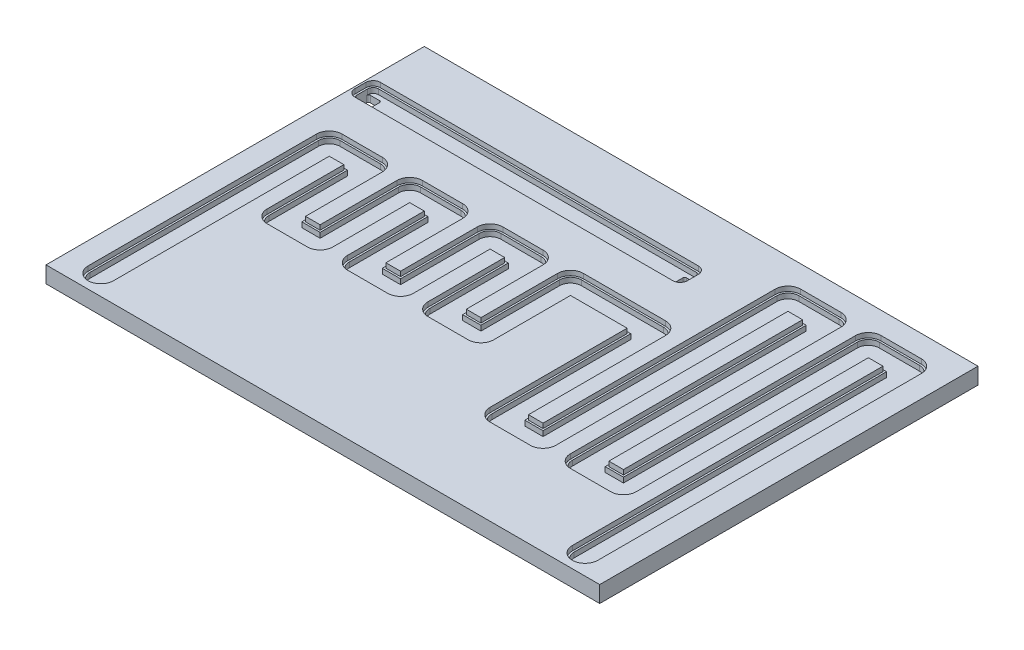
SolidWorks part; units mm, degrees
ref_plane "前视基准面" through (0, 0, 0) normal (0, 0, 1) x (1, 0, 0)
ref_plane "上视基准面" through (0, 0, 0) normal (0, 1, 0) x (1, 0, 0)
ref_plane "右视基准面" through (0, 0, 0) normal (1, 0, 0) x (0, 0, -1)
sketch "草图1" plane through (0, 0, 0) normal (0, 1, 0) x (1, 0, 0)
  line L0 (5, -195) -> (5, -165)
  line L1 (0, 0) -> (1515, 0)
  line L2 (0, 0) -> (0, -1035)
  line L3 (0, -1035) -> (1515, -1035)
  line L4 (1515, 0) -> (1515, -1035)
  line L5 (25, -145) -> (895, -145)
  line L6 (915, -165) -> (915, -195)
  line L7 (895, -215) -> (25, -215)
  line L8 (-125.9274, -180) -> (1036.3031, -180) construction
  line L9 (25, -150) -> (895, -150)
  line L10 (910, -165) -> (910, -195)
  line L11 (895, -210) -> (25, -210)
  line L12 (10, -195) -> (10, -165)
  line L13 (60, -980) -> (60, -355)
  line L14 (40, -197.5) -> (15, -197.5)
  line L15 (45, -192.5) -> (45, -167.5)
  line L16 (40, -162.5) -> (15, -162.5)
  line L17 (10, -192.5) -> (10, -167.5)
  line L18 (45, -197.5) -> (10, -162.5) construction
  line L19 (45, -162.5) -> (10, -197.5) construction
  line L20 (905, -197.5) -> (880, -197.5)
  line L21 (910, -192.5) -> (910, -167.5)
  line L22 (905, -162.5) -> (880, -162.5)
  line L23 (875, -192.5) -> (875, -167.5)
  line L24 (910, -197.5) -> (875, -162.5) construction
  line L25 (910, -162.5) -> (875, -197.5) construction
  line L26 (95, -320) -> (205, -320)
  line L27 (240, -355) -> (240, -565)
  line L28 (240, -565) -> (280, -565)
  line L29 (280, -565) -> (280, -355)
  line L30 (315, -320) -> (425, -320)
  line L31 (460, -355) -> (460, -565)
  line L32 (460, -565) -> (500, -565)
  line L33 (500, -565) -> (500, -355)
  line L34 (535, -320) -> (645, -320)
  line L35 (680, -355) -> (680, -565)
  line L36 (680, -565) -> (720, -565)
  line L37 (720, -565) -> (720, -355)
  line L38 (755, -320) -> (980, -320)
  line L39 (1015, -355) -> (1015, -730)
  line L40 (1015, -730) -> (1055, -730)
  line L41 (1055, -730) -> (1055, -95)
  line L42 (1090, -60) -> (1200, -60)
  line L43 (1235, -95) -> (1235, -730)
  line L44 (1235, -730) -> (1275, -730)
  line L45 (1275, -730) -> (1275, -95)
  line L46 (1310, -60) -> (1420, -60)
  line L47 (1455, -95) -> (1455, -980)
  line L48 (1455, -980) -> (1385, -980) construction
  line L49 (1385, -980) -> (1385, -130)
  line L50 (1385, -130) -> (1345, -130)
  line L51 (1345, -130) -> (1345, -765)
  line L52 (1310, -800) -> (1200, -800)
  line L53 (1165, -765) -> (1165, -130)
  line L54 (1165, -130) -> (1125, -130)
  line L55 (1125, -130) -> (1125, -765)
  line L56 (1090, -800) -> (980, -800)
  line L57 (945, -765) -> (945, -390)
  line L58 (945, -390) -> (790, -390)
  line L59 (790, -390) -> (790, -600)
  line L60 (755, -635) -> (645, -635)
  line L61 (610, -600) -> (610, -390)
  line L62 (610, -390) -> (570, -390)
  line L63 (570, -390) -> (570, -600)
  line L64 (535, -635) -> (425, -635)
  line L65 (390, -600) -> (390, -390)
  line L66 (390, -390) -> (350, -390)
  line L67 (350, -390) -> (350, -600)
  line L68 (315, -635) -> (205, -635)
  line L69 (170, -600) -> (170, -390)
  line L70 (170, -390) -> (130, -390)
  line L71 (130, -390) -> (130, -980)
  line L72 (130, -980) -> (60, -980) construction
  line L73 (1390, -980) -> (1390, -125)
  line L74 (1390, -125) -> (1340, -125)
  line L75 (1340, -125) -> (1340, -765)
  line L76 (1310, -795) -> (1200, -795)
  line L77 (1170, -765) -> (1170, -125)
  line L78 (1170, -125) -> (1120, -125)
  line L79 (1120, -125) -> (1120, -765)
  line L80 (1090, -795) -> (980, -795)
  line L81 (950, -765) -> (950, -385)
  line L82 (950, -385) -> (785, -385)
  line L83 (785, -385) -> (785, -600)
  line L84 (755, -630) -> (645, -630)
  line L85 (615, -600) -> (615, -385)
  line L86 (615, -385) -> (565, -385)
  line L87 (565, -385) -> (565, -600)
  line L88 (535, -630) -> (425, -630)
  line L89 (395, -600) -> (395, -385)
  line L90 (395, -385) -> (345, -385)
  line L91 (345, -385) -> (345, -600)
  line L92 (315, -630) -> (205, -630)
  line L93 (175, -600) -> (175, -385)
  line L94 (175, -385) -> (125, -385)
  line L95 (125, -385) -> (125, -980)
  line L96 (65, -980) -> (65, -355)
  line L97 (95, -325) -> (205, -325)
  line L98 (235, -355) -> (235, -570)
  line L99 (235, -570) -> (285, -570)
  line L100 (285, -570) -> (285, -355)
  line L101 (315, -325) -> (425, -325)
  line L102 (455, -355) -> (455, -570)
  line L103 (455, -570) -> (505, -570)
  line L104 (505, -570) -> (505, -355)
  line L105 (535, -325) -> (645, -325)
  line L106 (675, -355) -> (675, -570)
  line L107 (675, -570) -> (725, -570)
  line L108 (725, -570) -> (725, -355)
  line L109 (755, -325) -> (980, -325)
  line L110 (1010, -355) -> (1010, -735)
  line L111 (1010, -735) -> (1060, -735)
  line L112 (1060, -735) -> (1060, -95)
  line L113 (1090, -65) -> (1200, -65)
  line L114 (1230, -95) -> (1230, -735)
  line L115 (1230, -735) -> (1280, -735)
  line L116 (1280, -735) -> (1280, -95)
  line L117 (1310, -65) -> (1420, -65)
  line L118 (1450, -95) -> (1450, -980)
  arc A0 (5, -195) -> (25, -215) centre (25, -195) ccw
  arc A1 (5, -165) -> (25, -145) centre (25, -165) cw
  arc A2 (915, -195) -> (895, -215) centre (895, -195) cw
  arc A3 (895, -145) -> (915, -165) centre (895, -165) cw
  arc A4 (895, -150) -> (910, -165) centre (895, -165) cw
  arc A5 (910, -195) -> (895, -210) centre (895, -195) cw
  arc A6 (10, -195) -> (25, -210) centre (25, -195) ccw
  arc A7 (10, -165) -> (25, -150) centre (25, -165) cw
  arc A10 (205, -635) -> (170, -600) centre (205, -600) cw
  arc A11 (350, -600) -> (315, -635) centre (315, -600) cw
  arc A12 (425, -635) -> (390, -600) centre (425, -600) cw
  arc A13 (570, -600) -> (535, -635) centre (535, -600) cw
  arc A14 (645, -635) -> (610, -600) centre (645, -600) cw
  arc A15 (790, -600) -> (755, -635) centre (755, -600) cw
  arc A16 (980, -800) -> (945, -765) centre (980, -765) cw
  arc A17 (1125, -765) -> (1090, -800) centre (1090, -765) cw
  arc A18 (1200, -800) -> (1165, -765) centre (1200, -765) cw
  arc A19 (1345, -765) -> (1310, -800) centre (1310, -765) cw
  arc A20 (1420, -60) -> (1455, -95) centre (1420, -95) cw
  arc A21 (1275, -95) -> (1310, -60) centre (1310, -95) cw
  arc A22 (1200, -60) -> (1235, -95) centre (1200, -95) cw
  arc A23 (1055, -95) -> (1090, -60) centre (1090, -95) cw
  arc A24 (980, -320) -> (1015, -355) centre (980, -355) cw
  arc A25 (720, -355) -> (755, -320) centre (755, -355) cw
  arc A26 (645, -320) -> (680, -355) centre (645, -355) cw
  arc A27 (500, -355) -> (535, -320) centre (535, -355) cw
  arc A28 (425, -320) -> (460, -355) centre (425, -355) cw
  arc A29 (280, -355) -> (315, -320) centre (315, -355) cw
  arc A30 (205, -320) -> (240, -355) centre (205, -355) cw
  arc A31 (60, -355) -> (95, -320) centre (95, -355) cw
  arc A32 (1340, -765) -> (1310, -795) centre (1310, -765) cw
  arc A33 (1200, -795) -> (1170, -765) centre (1200, -765) cw
  arc A34 (1120, -765) -> (1090, -795) centre (1090, -765) cw
  arc A35 (980, -795) -> (950, -765) centre (980, -765) cw
  arc A36 (785, -600) -> (755, -630) centre (755, -600) cw
  arc A37 (645, -630) -> (615, -600) centre (645, -600) cw
  arc A38 (565, -600) -> (535, -630) centre (535, -600) cw
  arc A39 (425, -630) -> (395, -600) centre (425, -600) cw
  arc A40 (345, -600) -> (315, -630) centre (315, -600) cw
  arc A41 (205, -630) -> (175, -600) centre (205, -600) cw
  arc A42 (65, -355) -> (95, -325) centre (95, -355) cw
  arc A43 (205, -325) -> (235, -355) centre (205, -355) cw
  arc A44 (285, -355) -> (315, -325) centre (315, -355) cw
  arc A45 (425, -325) -> (455, -355) centre (425, -355) cw
  arc A46 (505, -355) -> (535, -325) centre (535, -355) cw
  arc A47 (645, -325) -> (675, -355) centre (645, -355) cw
  arc A48 (725, -355) -> (755, -325) centre (755, -355) cw
  arc A49 (980, -325) -> (1010, -355) centre (980, -355) cw
  arc A50 (1060, -95) -> (1090, -65) centre (1090, -95) cw
  arc A51 (1200, -65) -> (1230, -95) centre (1200, -95) cw
  arc A52 (1280, -95) -> (1310, -65) centre (1310, -95) cw
  arc A53 (1420, -65) -> (1450, -95) centre (1420, -95) cw
  arc A54 (60, -980) -> (130, -980) centre (95, -980) ccw
  arc A55 (1390, -980) -> (1450, -980) centre (1420, -980) ccw
  arc A56 (910, -167.5) -> (905, -162.5) centre (905, -167.5) ccw
  arc A57 (905, -197.5) -> (910, -192.5) centre (905, -192.5) ccw
  arc A58 (880, -197.5) -> (875, -192.5) centre (880, -192.5) cw
  arc A59 (880, -162.5) -> (875, -167.5) centre (880, -167.5) ccw
  arc A60 (15, -162.5) -> (10, -167.5) centre (15, -167.5) ccw
  arc A61 (15, -197.5) -> (10, -192.5) centre (15, -192.5) cw
  arc A62 (40, -197.5) -> (45, -192.5) centre (40, -192.5) ccw
  arc A63 (45, -167.5) -> (40, -162.5) centre (40, -167.5) ccw
  arc A65 (1385, -980) -> (1455, -980) centre (1420, -980) ccw
  arc A66 (65, -980) -> (125, -980) centre (95, -980) ccw
  point P31 (27.5, -180)
  point P36 (892.5, -180)
  point P89 (350, -495)
  point P90 (790, -495)
  point P91 (1035, -800)
  point P92 (150, -390)
  point P93 (280, -460)
  point P94 (1365, -60)
  point P95 (95, -980)
  point P96 (1420, -980)
  dimension "D7" = 20
  dimension "D51" = 35
  dimension "D55" = 5
  dimension "D54" = 35
  dimension "D1" = 1515
  dimension "D2" = 1035
  dimension "D3" = 180
  dimension "D4" = 70
  dimension "D5" = 5
  dimension "D6" = 910
  dimension "D9" = 35
  dimension "D10" = 35
  dimension "D11" = 35
  dimension "D12" = 35
  dimension "D13" = 865
  dimension "D14" = 60
  dimension "D15" = 70
  dimension "D16" = 70
  dimension "D17" = 70
  dimension "D18" = 70
  dimension "D19" = 70
  dimension "D20" = 70
  dimension "D21" = 70
  dimension "D22" = 70
  dimension "D23" = 70
  dimension "D24" = 70
  dimension "D25" = 70
  dimension "D26" = 70
  dimension "D27" = 400
  dimension "D28" = 70
  dimension "D29" = 70
  dimension "D30" = 70
  dimension "D31" = 70
  dimension "D32" = 70
  dimension "D33" = 245
  dimension "D34" = 70
  dimension "D35" = 70
  dimension "D36" = 295
  dimension "D37" = 40
  dimension "D38" = 40
  dimension "D39" = 40
  dimension "D40" = 40
  dimension "D41" = 40
  dimension "D42" = 40
  dimension "D43" = 40
  dimension "D44" = 40
  dimension "D45" = 40
  dimension "D46" = 40
  dimension "D47" = 235
  dimension "D48" = 975
  dimension "D49" = 55
  dimension "D50" = 55
  dimension "D52" = 5
  dimension "D8" = 5
extrude "凸台-拉伸1" add sketch "草图1" against normal blind 45 contours L3 L4 L1 L2
extrude "切除-拉伸1" cut sketch "草图1<3>" against normal blind 13 contours L7 A0 L0 A1 L5 A3 L6 A2
sketch "草图1<3>" plane through (0, 0, 0) normal (0, 1, 0) x (1, 0, 0) same geometry as "草图1"
extrude "切除-拉伸2" cut sketch "草图1<5>" against normal blind 27 contours L9 A4 L10 A5 L11 A6 L12 A7
sketch "草图1<5>" plane through (0, 0, 0) normal (0, 1, 0) x (1, 0, 0) same geometry as "草图1"
extrude "切除-拉伸3" cut sketch "草图1<6>" against normal blind 45 contours L15 A63 L16 A60 L17 A61 L14 A62 | L23 A59 L22 A56 L21 A57 L20 A58
sketch "草图1<6>" plane through (0, 0, 0) normal (0, 1, 0) x (1, 0, 0) same geometry as "草图1"
extrude "切除-拉伸5" cut sketch "草图1<9>" against normal blind 13 contours L71 A54 L13 A31 L26 A30 L27 L28 L29 A29 L30 A28 L31 L32 L33 A27 L34 A26 L35 L36 L37 A25 L38 A24 L39 L40 L41 A23 L42 A22 L43 L44 L45 A21 L46 A20 L47 A65 L49 L50 L51 A19 L52 A18 L53 L54 L55 A17 L56 A16 L57 L58 L59 A15 L60 A14 L61 L62 L63 A13 L64 A12 L65 L66 L67 A11 L68 A10 L69 L70
sketch "草图1<9>" plane through (0, 0, 0) normal (0, 1, 0) x (1, 0, 0) same geometry as "草图1"
extrude "切除-拉伸6" cut sketch "草图1<10>" against normal blind 27 contours L73 L74 L75 A32 L76 A33 L77 L78 L79 A34 L80 A35 L81 L82 L83 A36 L84 A37 L85 L86 L87 A38 L88 A39 L89 L90 L91 A40 L92 A41 L93 L94 L95 A66 L96 A42 L97 A43 L98 L99 L100 A44 L101 A45 L102 L103 L104 A46 L105 A47 L106 L107 L108 A48 L109 A49 L110 L111 L112 A50 L113 A51 L114 L115 L116 A52 L117 A53 L118 A55
sketch "草图1<10>" plane through (0, 0, 0) normal (0, 1, 0) x (1, 0, 0) same geometry as "草图1"
sketch "草图3" plane through (0, 0, 0) normal (0, 1, 0) x (1, 0, 0)
  line L0 (0, -1035) -> (1515, -1035) construction
  circle A0 centre (95, -990) radius 10.25
  circle A1 centre (1420, -990) radius 10.25
  point P2 (0, 0)
  point P9 (0, 0)
  dimension "D1" = 20.5
  dimension "D2" = 45
extrude "切除-拉伸7" cut sketch "草图3" against normal blind 45
